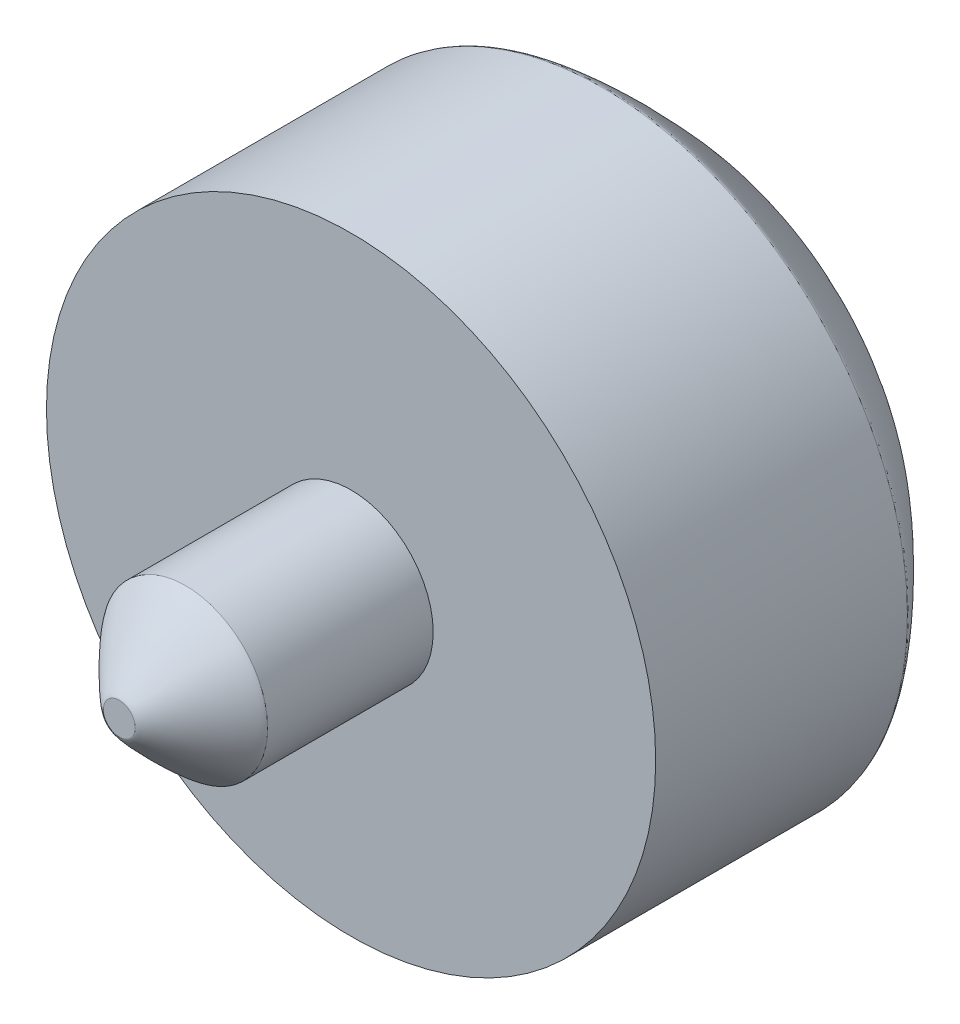
SolidWorks part; units mm, degrees
ref_plane "前视基准面" through (0, 0, 0) normal (0, 0, 1) x (1, 0, 0)
ref_plane "上视基准面" through (0, 0, 0) normal (0, 1, 0) x (1, 0, 0)
ref_plane "右视基准面" through (0, 0, 0) normal (1, 0, 0) x (0, 0, -1)
sketch "草图1" plane through (0, 0, 0) normal (0, 0, 1) x (1, 0, 0)
  circle A0 centre (0, 0) radius 4.6
extrude "凸台-拉伸1" add sketch "草图1" along normal blind 5
sketch "草图2" plane through (0, 0, 5) normal (0, 0, 1) x (1, 0, 0)
  circle A0 centre (0, 0) radius 1.24
extrude "凸台-拉伸2" add sketch "草图2" along normal blind 3.5
fillet "圆角1" radius 1 1 edges at (1.24, 0, 8.5) conic radius 10
fillet "圆角2" radius 1.2 1 edges at (4.6, 0, 0) conic radius 10
